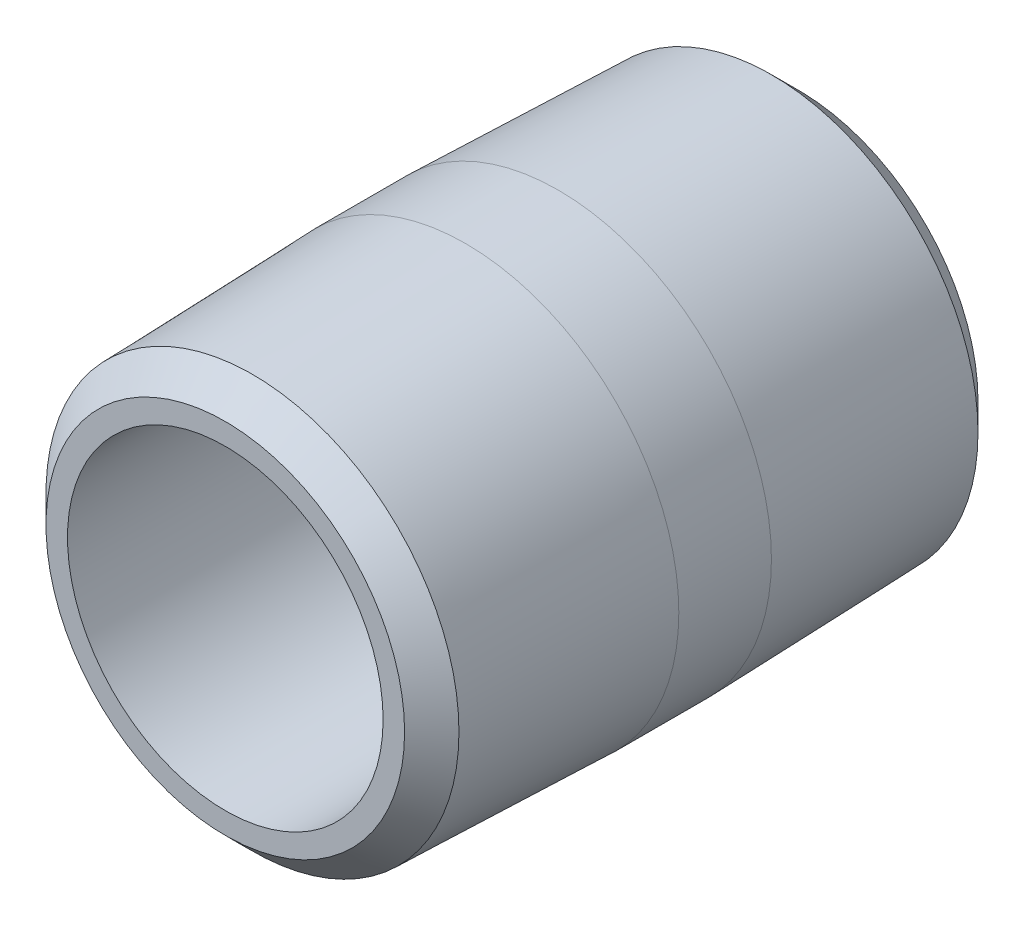
SolidWorks part; units mm, degrees
ref_plane "Front" through (0, 0, 0) normal (0, 0, 1) x (1, 0, 0)
ref_plane "Top" through (0, 0, 0) normal (0, 1, 0) x (1, 0, 0)
ref_plane "Right" through (0, 0, 0) normal (1, 0, 0) x (0, 0, -1)
sketch "Sketch1" plane through (0, 0, 0) normal (1, 0, 0) x (0, 0, -1)
  line L0 (-14.351, 0) -> (14.351, 0) construction
  line L1 (-14.351, 7.8994) -> (-14.351, 8.975)
  line L2 (-12.9903, 10.3357) -> (-2.3177, 10.668)
  line L3 (-2.3177, 10.668) -> (2.3177, 10.668)
  line L4 (-2.3177, 10.668) -> (-14.351, 10.668) construction
  line L5 (-14.351, 10.668) -> (-14.351, 8.975) construction
  line L6 (-12.9903, 10.3357) -> (-14.351, 8.975)
  line L7 (-14.351, 8.975) -> (-12.9903, 8.975) construction
  line L8 (-12.9903, 8.975) -> (-12.9903, 10.3357) construction
  line L9 (-12.9903, 10.3357) -> (-14.351, 10.2933) construction
  line L10 (-14.351, 10.2933) -> (-15.0314, 9.1149) construction
  line L11 (-15.0314, 9.1149) -> (-15.2581, 9.1149) construction
  line L12 (-15.2581, 9.1149) -> (-16.2331, 10.8036) construction
  line L13 (-16.2331, 10.8036) -> (-14.0564, 10.8036) construction
  line L14 (-14.0564, 10.8036) -> (-14.351, 10.2933) construction
  line L15 (-14.6912, 9.7041) -> (-15.5983, 9.7041) construction
  line L16 (-15.1447, 9.7041) -> (-15.1447, 9.1149) construction
  line L17 (-15.1447, 9.4095) -> (-16.959, 9.4095) construction
  line L18 (-14.351, 7.8994) -> (14.351, 7.8994)
  line L19 (0, 0) -> (0, 10.668) construction
  line L20 (14.351, 7.8994) -> (14.351, 8.975)
  line L21 (12.9903, 10.3357) -> (14.351, 8.975)
  line L22 (12.9903, 10.3357) -> (2.3177, 10.668)
  line L23 (12.9903, -10.3357) -> (2.3177, -10.668) construction
  line L24 (-2.3177, -10.668) -> (2.3177, -10.668) construction
  line L25 (-12.9903, -10.3357) -> (-2.3177, -10.668) construction
  line L26 (-4.3724, -10.604) -> (-4.3724, 0) construction
  line L27 (4.3724, -10.604) -> (4.3724, 0) construction
  point P27 (0, 7.8994)
  dimension "D1" = 1.783
  dimension "D2" = 1.3607
  dimension "D3" = 0.2268
  dimension "D4" = 0.9071
  dimension "D5" = 60
  dimension "D6" = 9.9786
revolve "Revolve1" add sketch "Sketch1" angle 360 about L0
sketch "Sketch2" plane through (0, 0, 0) normal (0, 0, 1) x (1, 0, 0)
  line L0 (-10.668, 0) -> (-7.8994, 0) construction
  line L1 (-7.8994, 0) -> (7.8994, 0) construction
  line L2 (7.8994, 0) -> (10.668, 0) construction
  circle A0 centre (0, 0) radius 7.8994 construction
  circle A1 centre (0, 0) radius 10.668 construction
  circle A2 centre (0, 0) radius 7.8994 construction
  circle A3 centre (0, 0) radius 10.668 construction
sketch "Sketch3" plane through (0, 0, 14.351) normal (0, 0, 1) x (1, 0, 0)
  circle A0 centre (0, 0) radius 10.2933
curve "Helix/Spiral1"
sketch "Sketch4" [suppressed] plane through (0, 0, 0) normal (1, 0, 0) x (0, 0, -1)
  line L0 (-16.2331, 10.8036) -> (-15.2581, 9.1149)
  line L1 (-15.2581, 9.1149) -> (-15.0314, 9.1149)
  line L2 (-15.0314, 9.1149) -> (-14.0564, 10.8036)
  line L3 (-14.0564, 10.8036) -> (-16.2331, 10.8036)
sweep "Sweep1" [suppressed] add profiles "Sketch4" path "Helix/Spiral1"
sketch "Sketch5" [suppressed] plane through (0, 0, 0) normal (1, 0, 0) x (0, 0, -1)
  line L0 (-14.351, 0) -> (14.351, 0) construction
  line L1 (14.351, -8.8537) -> (-2.3177, -8.8537)
  line L2 (14.351, -8.8537) -> (14.351, 8.8537)
  line L3 (14.351, 8.8537) -> (-2.3177, 8.8537)
  line L4 (-2.3177, -8.8537) -> (-2.3177, 8.8537)
  line L5 (14.351, -8.8537) -> (-2.3177, 8.8537) construction
  line L6 (14.351, 8.8537) -> (-2.3177, -8.8537) construction
  line L7 (-2.3177, 10.668) -> (2.3177, 10.668) construction
  line L8 (14.351, -8.975) -> (14.351, 8.975) construction
  point P0 (6.0166, 0)
  dimension "D1" = 1.8143
extrude "Cut-Extrude1" [suppressed] cut sketch "Sketch5" against normal through all both and the other way through all
ref_axis "Axis1" [suppressed] through (0, 0, 0) along (0, 1, 0)
pattern_circular "CirPattern1" [suppressed] count 2 over 180 about axis through (0, 0, 0) along (0, 1, 0) of bodies 111
combine bodies "Combine1" [suppressed] operation type subtract main body 109 bodies to subtract 111 112
sketch "Sketch6" [suppressed] plane through (0, 0, 0) normal (1, 0, 0) x (0, 0, -1)
  line L0 (-2.3177, 10.668) -> (-10.482, 7.8994)
  line L1 (-14.351, 7.8994) -> (14.351, 7.8994) construction
  line L2 (-10.482, 7.8994) -> (10.482, 7.8994)
  line L3 (-2.3177, 10.668) -> (2.3177, 10.668)
  line L4 (-2.3177, 10.668) -> (2.3177, 10.668) construction
  line L5 (0, 10.668) -> (0, 7.8994) construction
  line L6 (2.3177, 10.668) -> (10.482, 7.8994)
  line L7 (-14.351, 0) -> (14.351, 0) construction
  dimension "D1" = 8.1643
revolve "Revolve2" [suppressed] add sketch "Sketch6" angle 360 about L7
equation "\"D3@Sketch1\"=\"Pitch@Sketch1\"*.125"
equation "\"D4@Sketch1\"=\"Pitch@Sketch1\"*.5"
equation "\"D2@Sketch1\"=\"Pitch@Sketch1\"*.75"
equation "\"D4@Helix/Spiral1\"=\"Pitch@Sketch1\""
equation "\"D3@Helix/Spiral1\"=\"ThreadLength@Sketch1\"+\"Pitch@Sketch1\""
equation "\"D1@Sketch5\"=\"Pitch@Sketch1\""
equation "\"D1@Sketch6\"=\"Pitch@Sketch1\"*4.5"
equation "\"D6@Sketch1\"=\"Pitch@Sketch1\"*5.5"
equation "\"ThreadLength@Sketch1\"=0.59375000-.12"
